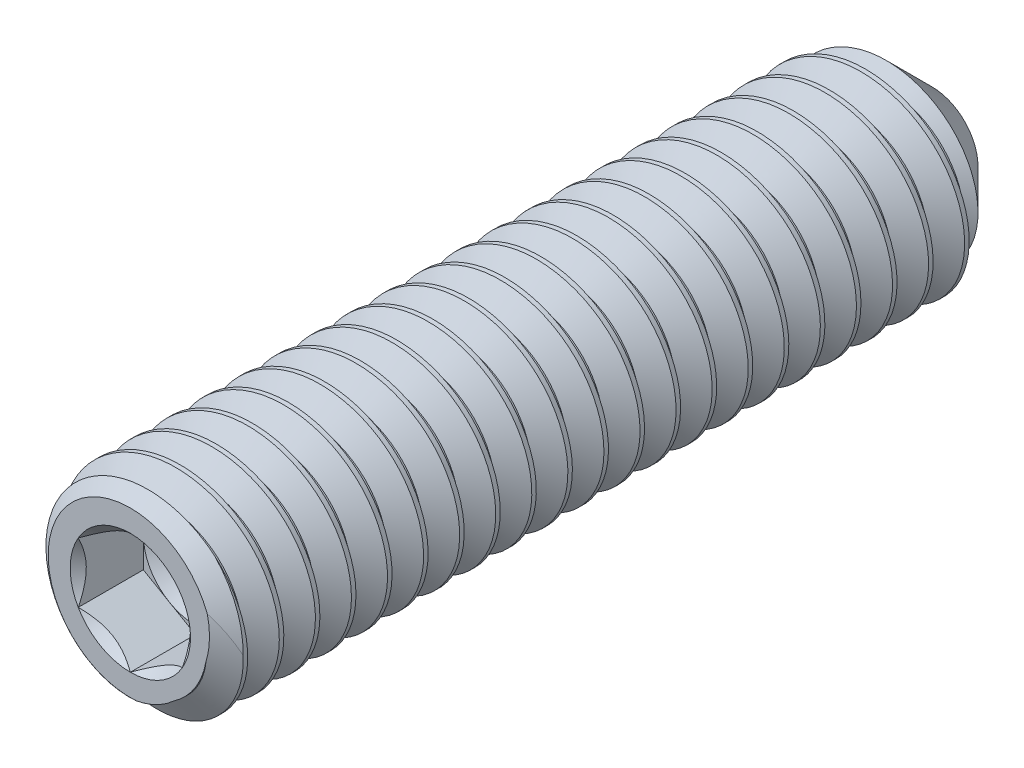
SolidWorks part; units mm, degrees
other "Imported1" parameters "D3"=11, "D1"=46.842, "Length"=10, "Drive Size"=1.3, "Thread Size"=2.5, "Thread Pitch"=0.45, "D2"=0.0866, "hex Depth"=0.8125, "Dia"=12, "D4"=2.3829, "Cup Point Dia"=3.3528, "D5"=1.436, "D6"=1.4986, "D7"=5.0014, "Pitch"=1.75
ref_plane "Front" through (0, 0, 0) normal (0, 0, 1) x (1, 0, 0)
ref_plane "Top" through (0, 0, 0) normal (0, 1, 0) x (1, 0, 0)
ref_plane "Right" through (0, 0, 0) normal (1, 0, 0) x (0, 0, -1)
sketch "Sketch1" plane through (0, 0, 0) normal (1, 0, 0) x (0, 0, -1)
  line L0 (5, 1.25) -> (-5, 1.25) construction
  line L1 (-5, 1.25) -> (-5, -1.25) construction
  line L2 (-5, -1.25) -> (5, -1.25) construction
  line L3 (5, -1.25) -> (5, 1.25) construction
  line L4 (-5, 0.65) -> (-5, -0.65) construction
  line L5 (4.9719, 1.2987) -> (5.4219, 1.2987) construction
  line L6 (4.9719, 1.2987) -> (5, 1.25) construction
  line L7 (5, 1.25) -> (5.3938, 1.25) construction
  line L8 (5.3938, 1.25) -> (5.4219, 1.2987) construction
  line L9 (5, 1.25) -> (5.1969, 0.909) construction
  line L10 (5.1969, 0.909) -> (5.3938, 1.25) construction
  line L11 (5.1687, 0.9577) -> (5.225, 0.9577) construction
  line L12 (5.1969, 1.2987) -> (5.1969, 1.25) construction
  line L13 (5.1969, 0.9577) -> (5.1969, 0.909) construction
  point P3 (0, 1.25)
  point P24 (-5, 0)
  point P25 (-5, 0)
  dimension "D1" = 0.0563
sketch "Sketch11" plane through (0, 0, 0) normal (1, 0, 0) x (0, 0, -1)
  line L0 (-5, 0) -> (-5, 1.025)
  line L1 (-5, 1.025) -> (-4.8425, 1.25)
  line L2 (-4.8425, 1.25) -> (4.325, 1.25)
  line L3 (4.325, 1.25) -> (5, 0.575)
  line L4 (5, 0.575) -> (4.6545, 0)
  line L5 (4.6545, 0) -> (-5, 0)
  line L6 (4.6545, 0) -> (5, 0) construction
  line L7 (5, 0) -> (5, 0.575) construction
  line L8 (5, -0.575) -> (4.6545, 0) construction
  line L9 (-4.8425, -1.25) -> (4.325, -1.25) construction
  line L10 (-5, -1.25) -> (5, -1.25) construction
  line L11 (-5, 1.25) -> (-5, -1.25) construction
  line L12 (5, -1.25) -> (5, 1.25) construction
  point P11 (3.425, -1.25)
  point P12 (-5, 1.25)
  dimension "D3" = 35
  dimension "D5" = 118
  dimension "D6" = 45
  dimension "D1" = 0.225
  dimension "D2" = 1.575
  dimension "D4" = 0.675
revolve "Revolve1" add sketch "Sketch11" angle 360 about L6
sketch "Sketch2" plane through (0, 0, 5) normal (0, 0, 1) x (1, 0, 0)
  line L1 (0, 0.7506) -> (-0.65, 0.3753)
  line L2 (-0.65, 0.3753) -> (-0.65, -0.3753)
  line L3 (-0.65, -0.3753) -> (0, -0.7506)
  line L4 (0, -0.7506) -> (0.65, -0.3753)
  line L5 (0.65, -0.3753) -> (0.65, 0.3753)
  line L6 (0.65, 0.3753) -> (0, 0.7506)
  circle A0 centre (0, 0) radius 0.65 construction
  circle A1 centre (0, 0) radius 1.25 construction
extrude "Cut-Extrude1" cut sketch "Sketch2" against normal blind 0.8125
sketch "Sketch3" plane through (0, 0, 5) normal (0, 0, 1) x (1, 0, 0)
  circle A0 centre (0, 0) radius 0.7506
extrude "Cut-Extrude2" cut sketch "Sketch3" against normal through all draft 45
sketch "Sketch4" plane through (0, 0, 4.1875) normal (0, 0, 1) x (1, 0, 0)
  circle A0 centre (0, 0) radius 0.65 construction
  circle A1 centre (0, 0) radius 0.65
extrude "Cut-Extrude3" cut sketch "Sketch4" against normal through all draft 60
sketch "Sketch13" plane through (0, 0, 0) normal (1, 0, 0) x (0, 0, -1)
  line L0 (0, -1.25) -> (0, 1.25) construction
  line L2 (-4.8425, 1.25) -> (4.325, 1.25) construction
  line L4 (4.6545, 0) -> (-5, 0) construction
  point P0 (2.1545, 0)
  point P4 (0, 0)
  point P9 (-2.1545, 0)
  dimension "D1" = 2.5
ref_plane "Plane1" through (0, 0, -5) normal (0, 0, 1) x (1, 0, 0)
sketch "Sketch5" plane through (0, 0, -5) normal (0, 0, 1) x (1, 0, 0)
  circle A0 centre (0, 0) radius 1.25 construction
  circle A1 centre (0, 0) radius 1.25
curve "Helix/Spiral1" pitch 0.45 height 11 radius 1.25 centre (0, 0, -5) axis (0, 0, 1) start towards (0, 1, 0)
sketch "Sketch6" plane through (0, 0, 0) normal (1, 0, 0) x (0, 0, -1)
  line L0 (4.9859, 1.2744) -> (5.4078, 1.2744)
  line L1 (4.9719, 1.2987) -> (5, 1.25) construction
  line L2 (5.3938, 1.25) -> (5.4219, 1.2987) construction
  line L3 (5.4078, 1.2744) -> (5.225, 0.9577)
  line L4 (5.225, 0.9577) -> (5.1687, 0.9577)
  line L5 (5.1687, 0.9577) -> (4.9859, 1.2744)
sweep "Cut-Sweep1" cut profiles "Sketch6" path "Helix/Spiral1"
equation "\"D3@Helix/Spiral1\" = \"Length@Sketch1\" * 1.1"
equation "\"hex Depth@Cut-Extrude1\"=\"Drive Size@Sketch1\" * .625"
equation "\"D1@Sketch11\" = \"Thread Pitch@Sketch1\" * .5"
equation "\"D2@Sketch11\" = \"Thread Pitch@Sketch1\" * 3.5"
equation "\"D1@Helix/Spiral1\" = \"Thread Pitch@Sketch1\""
equation "\"D4@Sketch11\" = \"Thread Pitch@Sketch1\" * 1.5"
equation "\"D1@Sketch1\" = \"Thread Pitch@Sketch1\" / 8"
equation "\"D1@Sketch13\"=\"Thread Size@Sketch1\""
